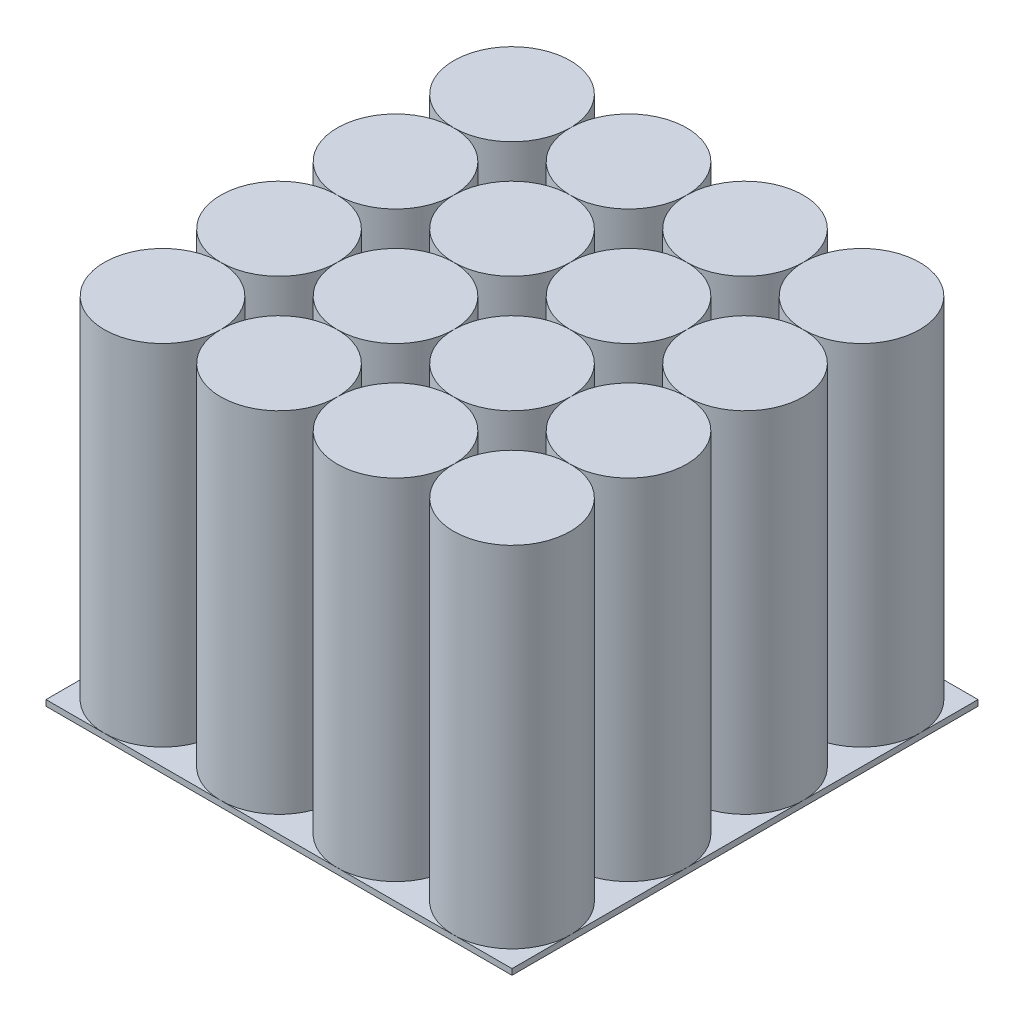
SolidWorks part; units mm, degrees
note: The reader was unsure of these and kept them because the rebuilt part matched: shared geometry of "Sketch1<5>".
ref_plane "Front Plane" through (0, 0, 0) normal (0, 0, 1) x (1, 0, 0)
ref_plane "Top Plane" through (0, 0, 0) normal (0, 1, 0) x (1, 0, 0)
ref_plane "Right Plane" through (0, 0, 0) normal (1, 0, 0) x (0, 0, -1)
sketch "Sketch1" plane through (0, 0, 0) normal (0, 1, 0) x (1, 0, 0)
  line L0 (0, 0) -> (0, -4.1593) construction
  line L1 (0, 0) -> (8, 0)
  line L2 (0, 0) -> (0, 8)
  line L3 (0, 8) -> (8, 8)
  line L4 (8, 0) -> (8, 8)
  circle A0 centre (1, 7) radius 1
  circle A1 centre (3, 7) radius 1
  circle A2 centre (5, 7) radius 1
  circle A3 centre (7, 7) radius 1
  circle A4 centre (1, 5) radius 1
  circle A5 centre (3, 5) radius 1
  circle A6 centre (5, 5) radius 1
  circle A7 centre (7, 5) radius 1
  circle A8 centre (1, 3) radius 1
  circle A9 centre (3, 3) radius 1
  circle A10 centre (5, 3) radius 1
  circle A11 centre (7, 3) radius 1
  circle A12 centre (1, 1) radius 1
  circle A13 centre (3, 1) radius 1
  circle A14 centre (5, 1) radius 1
  circle A15 centre (7, 1) radius 1
  dimension "D3" = 2
  dimension "D1" = 8
  dimension "D2" = 8
  dimension "D4" = 4
extrude "Boss-Extrude1" add sketch "Sketch1" against normal blind 0.1 contours A13 A9 A8 A12 | A12 | A8 | L1 L4 L3 L2
extrude "Boss-Extrude6" add sketch "Sketch1<5>" along normal blind 6 separate body contours A6 | A2 | A0 | A1 | A5 | A4 | A8 | A12 | A13 | A9 | A14 | A10 | A15 | A11 | A7 | A3
sketch "Sketch1<5>" plane through (0, 0, 0) normal (0, 1, 0) x (1, 0, 0) same geometry as "Sketch1"
